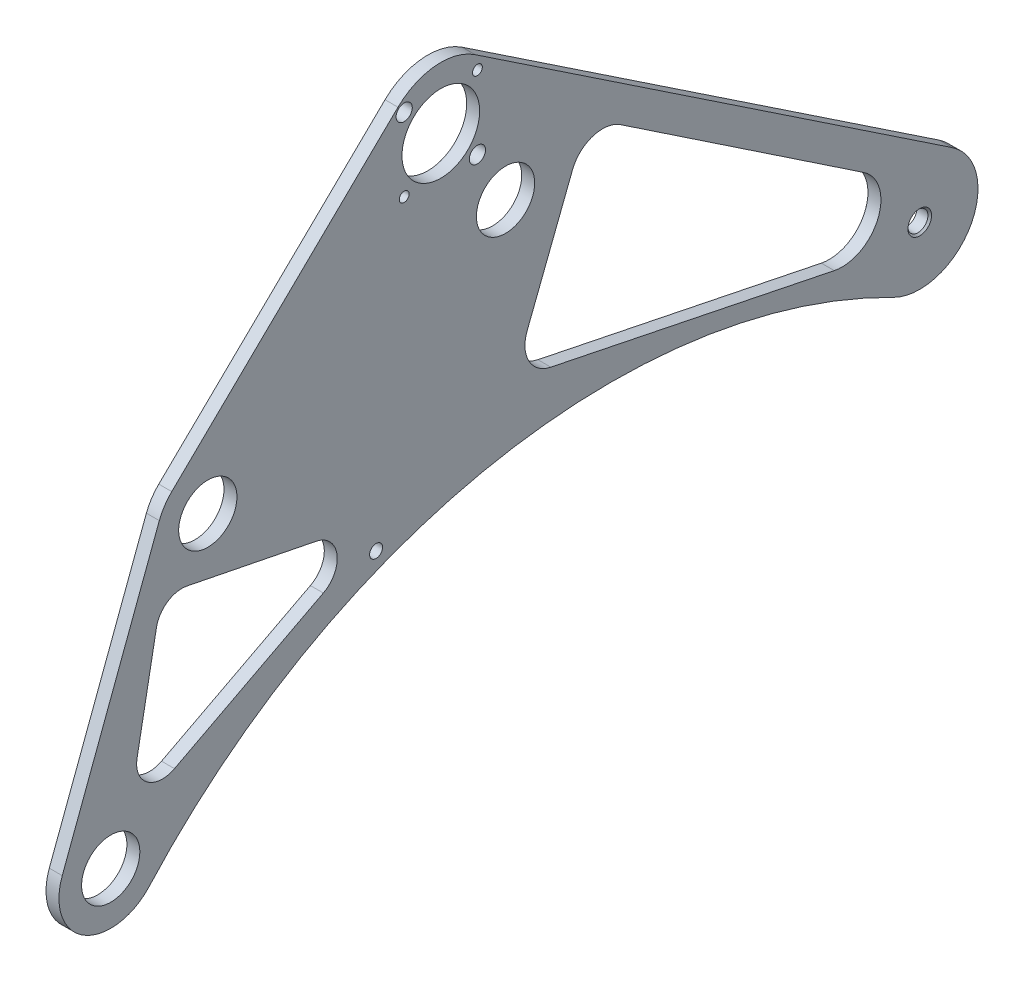
SolidWorks part; units mm, degrees
material "Acrylic (Medium-high impact)"
ref_plane "Front Plane" through (0, 0, 0) normal (0, 0, 1) x (1, 0, 0)
ref_plane "Top Plane" through (0, 0, 0) normal (0, 1, 0) x (1, 0, 0)
ref_plane "Right Plane" through (0, 0, 0) normal (1, 0, 0) x (0, 0, -1)
sketch "Sketch1" plane through (0, 0, 0) normal (1, 0, 0) x (0, 0, -1)
  line L0 (-548.7618, -304.8) -> (152.435, -304.8)
  line L1 (-192.8252, -101.6) -> (-152.4, -101.6)
  line L2 (-234.95, -143.7248) -> (-234.95, -186.4752)
  line L3 (-192.8252, -228.6) -> (-152.4, -228.6)
  line L4 (-152.4, -101.6) -> (-152.4, -228.6)
  circle A1 centre (0, 0) radius 6.35
  circle A6 centre (-396.875, -76.2) radius 9.525
  circle A7 centre (-349.25, 50.8) radius 9.525
  circle A8 centre (-203.2, 111.125) radius 9.525
  arc A9 (-234.95, -186.4752) -> (-192.8252, -228.6) centre (-192.8252, -186.4752) ccw
  arc A10 (-192.8252, -101.6) -> (-234.95, -143.7248) centre (-192.8252, -143.7248) ccw
  circle A11 centre (-355.7611, -180.5063) radius 120.65
  circle A12 centre (-234.95, 155.194) radius 29.845
  dimension "D1" = 12.7
  dimension "D2" = 19.05
  dimension "D3" = 42.1248
  dimension "D4" = 127
  dimension "D7" = 203.2
  dimension "D6" = 241.3
  dimension "D16" = 59.69
  dimension "D5" = 82.55
  dimension "D8" = 304.8
  dimension "D9" = 152.4
  dimension "D10" = 396.875
  dimension "D11" = 76.2
  dimension "D12" = 349.25
  dimension "D13" = 50.8
  dimension "D14" = 203.2
  dimension "D15" = 111.125
  dimension "D17" = 234.95
  dimension "D18" = 155.194
sketch "Sketch2" plane through (0, 0, 0) normal (1, 0, 0) x (0, 0, -1)
  line L1 (-420.6578, -67.2815) -> (-373.0328, 59.7185)
  line L3 (-366.9483, 69.0189) -> (-255.9667, 176.829)
  line L5 (-218.1841, 180.2675) -> (15.8835, 23.7539)
  line L6 (-1001.8623, -101.6) -> (216.545, -101.6) construction
  line L7 (-1029.8132, 185.3565) -> (188.5941, 185.3565) construction
  arc A0 (-366.9483, 69.0189) -> (-373.0328, 59.7185) centre (-349.25, 50.8) ccw
  arc A2 (-420.6578, -67.2815) -> (-377.9906, -93.1865) centre (-396.875, -76.2) ccw
  arc A4 (-218.1841, 180.2675) -> (-255.9667, 176.829) centre (-234.95, 155.194) ccw
  arc A5 (-12.9753, -25.4592) -> (15.8835, 23.7539) centre (0, 0) ccw
  arc A8 (-377.9906, -93.1865) -> (-12.9753, -25.4592) centre (-151.3783, -297.0244) cw
  circle A12 centre (-396.875, -76.2) radius 9.525 construction
  circle A13 centre (-349.25, 50.8) radius 9.525 construction
  dimension "D1" = 25.4
  dimension "D2" = 57.15
  dimension "D3" = 60.325
  dimension "D4" = 304.8
  dimension "D6" = 286.9565
extrude "Boss-Extrude1" add sketch "Sketch2" along normal blind 6.35
sketch "Sketch3" plane through (6.35, 0, 0) normal (1, 0, 0) x (0, 0, -1)
  line L0 (-216.9895, 173.1545) -> (-252.9105, 137.2335) construction
  line L1 (-234.95, 155.194) -> (-234.95, 205.0182) construction
  line L2 (-252.9105, 173.1545) -> (-216.9895, 137.2335) construction
  circle A0 centre (-203.2, 111.125) radius 14.2875
  circle A1 centre (-349.25, 50.8) radius 14.2875
  circle A2 centre (-396.875, -76.2) radius 14.2875
  circle A3 centre (-234.95, 155.194) radius 19.05
  circle A5 centre (-252.9105, 137.2335) radius 2.413
  circle A7 centre (-216.9895, 137.2335) radius 3.9687
  circle A8 centre (-216.9895, 173.1545) radius 2.413
  circle A9 centre (-252.9105, 173.1545) radius 3.9687
  point P18 (-234.95, 155.194)
  point P28 (-234.95, 155.194)
  dimension "D1" = 38.1
  dimension "D2" = 28.575
  dimension "D3" = 4.826
  dimension "D4" = 50.8
  dimension "D5" = 45
  dimension "D6" = 7.9375
  dimension "D7" = 50.8
extrude "Cut-Extrude1" cut sketch "Sketch3" against normal up to next
hole_wizard "3/8 Clearance Hole2" positions "Sketch7" profile "Sketch8" hole size "3/8" standard "ANSI Inch" end condition through all
sketch "Sketch7" plane through (6.35, 0, 0) normal (1, 0, 0) x (0, 0, -1)
  point P0 (0, 0)
sketch "Sketch8" plane through (6.35, 0, 0) normal (0, 1, 0) x (0, 0, -1)
  line L0 (0, 0) -> (0, 6.35)
  line L1 (0, 6.35) -> (4.9022, 6.35)
  line L2 (4.9022, 6.35) -> (4.9022, 0.8915)
  line L3 (4.9022, 0.8915) -> (5.7937, 0)
  line L5 (5.7937, 0) -> (0, 0)
  line L6 (-4.9022, 0.8915) -> (-5.7937, 0) construction
  line L11 (0, -6.35) -> (0, 107.95) construction
  dimension "Thru Hole Dia." = 9.8044
  dimension "Thru Hole Depth" = 6.35
  dimension "Near C'Sink Dia." = 11.5875
  dimension "Near C'Sink Angle" = 90
sketch "Sketch9" plane through (6.35, 0, 0) normal (1, 0, 0) x (0, 0, -1)
  line L0 (-495.9857, -101.6) -> (27.4607, -101.6) construction
  line L1 (100.4878, 185.3565) -> (-422.9585, 185.3565) construction
  arc A0 (-218.1841, 180.2675) -> (-255.9667, 176.829) centre (-234.95, 155.194) ccw construction
  arc A1 (-420.6578, -67.2815) -> (-377.9906, -93.1865) centre (-396.875, -76.2) ccw construction
  dimension "D1" = 286.9565
hole_wizard "1/4 (0.2500) Dowel Hole2" positions "Sketch12" profile "Sketch13" hole size "1/4" standard "ANSI Inch" end condition through all
sketch "Sketch12" plane through (6.35, 0, 0) normal (1, 0, 0) x (0, 0, -1)
  point P0 (-266.7, -6.35)
  dimension "D1" = 266.7
sketch "Sketch13" plane through (6.35, -6.35, 266.7) normal (0, 1, 0) x (0, 0, -1)
  line L0 (0, 0) -> (0, 6.35)
  line L1 (0, 6.35) -> (3.175, 6.35)
  line L2 (3.175, 6.35) -> (3.175, 0)
  line L5 (3.175, 0) -> (0, 0)
  line L11 (0, -6.35) -> (0, 107.95) construction
  dimension "Thru Hole Dia." = 6.35
  dimension "Thru Hole Depth" = 6.35
sketch "Sketch14" plane through (6.35, 0, 0) normal (1, 0, 0) x (0, 0, -1)
  line L0 (-365.6004, -49.3596) -> (-292.5754, -11.2596)
  line L1 (-295.9593, 12.4534) -> (-359.4593, 25.1534)
  line L2 (-374.4325, 15.0405) -> (-383.9575, -35.7595)
  line L3 (-146.7372, 114.7875) -> (-27.4946, 34.8749)
  line L4 (-41.926, 0.3882) -> (-180.9883, 28.8985)
  line L5 (-170.3706, 107.3538) -> (-192.5956, 50.2038)
  arc A0 (-383.9575, -35.7595) -> (-365.6004, -49.3596) centre (-371.475, -38.1) ccw
  arc A1 (-292.5754, -11.2596) -> (-295.9593, 12.4534) centre (-298.45, 0) ccw
  arc A2 (-359.4593, 25.1534) -> (-374.4325, 15.0405) centre (-361.95, 12.7) ccw
  circle A3 centre (-396.875, -76.2) radius 14.2875 construction
  circle A4 centre (-349.25, 50.8) radius 14.2875 construction
  circle A5 centre (-266.7, -6.35) radius 3.175 construction
  arc A6 (-41.926, 0.3882) -> (-27.4946, 34.8749) centre (-38.1, 19.05) ccw
  arc A7 (-192.5956, 50.2038) -> (-180.9883, 28.8985) centre (-177.8, 44.45) ccw
  arc A8 (-146.7372, 114.7875) -> (-170.3706, 107.3538) centre (-155.575, 101.6) ccw
  circle A10 centre (-203.2, 111.125) radius 14.2875 construction
  point P21 (0, 0)
  point P44 (-252.3055, -68.9946)
  point P45 (-16.4292, -38.1)
  point P46 (-292.5754, -51.5464)
  dimension "D1" = 38.1
  dimension "D2" = 25.4
  dimension "D3" = 25.4
  dimension "D4" = 38.1
  dimension "D5" = 12.7
  dimension "D6" = 31.75
  dimension "D7" = 6.35
  dimension "D8" = 25.4
  dimension "D9" = 38.1
  dimension "D12" = 31.75
  dimension "D13" = 47.625
  dimension "D14" = 9.525
  dimension "D15" = 139.7
  dimension "D16" = 25.4
  dimension "D10" = 38.1
  dimension "D11" = 19.05
extrude "Cut-Extrude2" cut sketch "Sketch14" against normal through all
